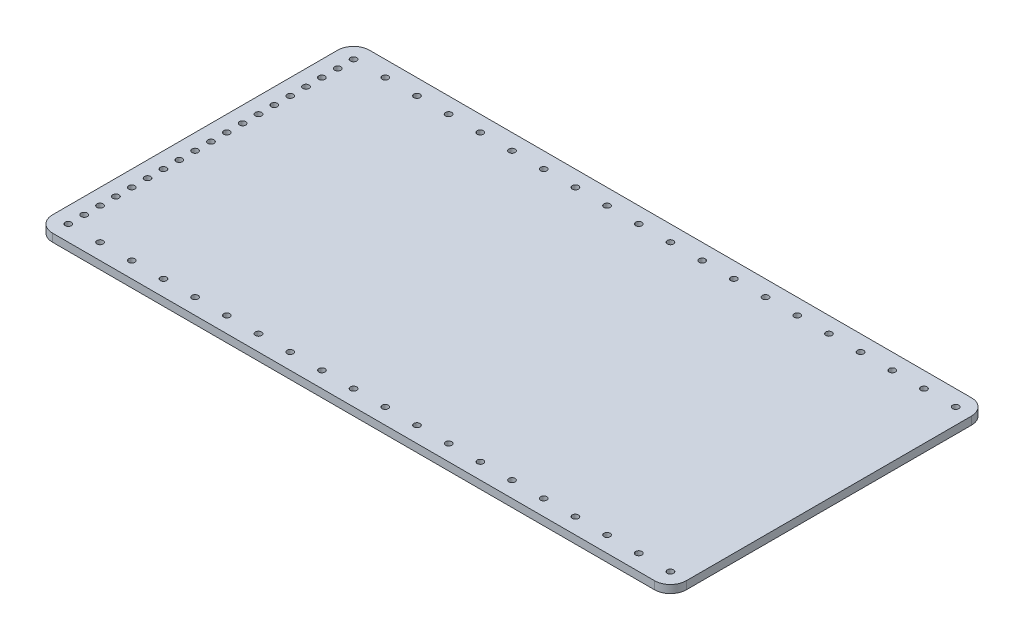
SolidWorks part; units mm, degrees
material "PC High Viscosity"
ref_plane "Front Plane" through (0, 0, 0) normal (0, 0, 1) x (1, 0, 0)
ref_plane "Top Plane" through (0, 0, 0) normal (0, 1, 0) x (1, 0, 0)
ref_plane "Right Plane" through (0, 0, 0) normal (1, 0, 0) x (0, 0, -1)
sketch "Sketch1" plane through (0, 0, 0) normal (0, 1, 0) x (1, 0, 0)
  line L1 (0, 0) -> (508, 0)
  line L2 (0, 0) -> (0, 254)
  line L3 (0, 254) -> (508, 254)
  line L4 (508, 0) -> (508, 254)
  dimension "D1" = 508
  dimension "D2" = 254
extrude "Boss-Extrude1" add sketch "Sketch1" along normal blind 6.35
sketch "Sketch3" plane through (0, 6.35, 0) normal (0, 1, 0) x (1, 0, 0)
  line L0 (508, 254) -> (0, 254) construction
  line L1 (0, 254) -> (0, 0) construction
  line L2 (12.7, 241.3) -> (38.1, 241.3) construction
  line L3 (12.7, 241.3) -> (12.7, 228.6) construction
  line L4 (12.7, 12.7) -> (38.1, 12.7) construction
  line L5 (12.7, 215.9) -> (12.7, 190.5) construction
  line L6 (495.3, 241.3) -> (495.3, 228.6) construction
  circle A0 centre (12.7, 241.3) radius 2.4892
  circle A1 centre (38.1, 241.3) radius 2.4892
  circle A2 centre (63.5, 241.3) radius 2.4892
  circle A3 centre (88.9, 241.3) radius 2.4892
  circle A4 centre (114.3, 241.3) radius 2.4892
  circle A5 centre (139.7, 241.3) radius 2.4892
  circle A6 centre (165.1, 241.3) radius 2.4892
  circle A7 centre (190.5, 241.3) radius 2.4892
  circle A8 centre (215.9, 241.3) radius 2.4892
  circle A9 centre (241.3, 241.3) radius 2.4892
  circle A10 centre (266.7, 241.3) radius 2.4892
  circle A11 centre (292.1, 241.3) radius 2.4892
  circle A12 centre (317.5, 241.3) radius 2.4892
  circle A13 centre (342.9, 241.3) radius 2.4892
  circle A14 centre (368.3, 241.3) radius 2.4892
  circle A15 centre (393.7, 241.3) radius 2.4892
  circle A16 centre (419.1, 241.3) radius 2.4892
  circle A17 centre (444.5, 241.3) radius 2.4892
  circle A18 centre (469.9, 241.3) radius 2.4892
  circle A19 centre (495.3, 241.3) radius 2.4892
  circle A23 centre (12.7, 228.6) radius 2.4892
  circle A24 centre (12.7, 215.9) radius 2.4892
  circle A25 centre (12.7, 203.2) radius 2.4892
  circle A26 centre (12.7, 190.5) radius 2.4892
  circle A27 centre (12.7, 177.8) radius 2.4892
  circle A28 centre (12.7, 165.1) radius 2.4892
  circle A29 centre (12.7, 152.4) radius 2.4892
  circle A30 centre (12.7, 139.7) radius 2.4892
  circle A31 centre (12.7, 127) radius 2.4892
  circle A32 centre (12.7, 114.3) radius 2.4892
  circle A33 centre (12.7, 101.6) radius 2.4892
  circle A56 centre (12.7, 215.9) radius 2.4892
  circle A57 centre (12.7, 190.5) radius 2.4892
  circle A58 centre (12.7, 165.1) radius 2.4892
  circle A59 centre (12.7, 139.7) radius 2.4892
  circle A60 centre (12.7, 114.3) radius 2.4892
  circle A61 centre (12.7, 88.9) radius 2.4892
  circle A62 centre (12.7, 63.5) radius 2.4892
  circle A63 centre (12.7, 38.1) radius 2.4892
  circle A64 centre (12.7, 12.7) radius 2.4892
  circle A65 centre (12.7, 88.9) radius 2.4892
  circle A66 centre (12.7, 76.2) radius 2.4892
  circle A67 centre (12.7, 63.5) radius 2.4892
  circle A68 centre (12.7, 50.8) radius 2.4892
  circle A69 centre (12.7, 38.1) radius 2.4892
  circle A70 centre (12.7, 25.4) radius 2.4892
  circle A71 centre (12.7, 12.7) radius 2.4892
  circle A72 centre (38.1, 12.7) radius 2.4892
  circle A73 centre (63.5, 12.7) radius 2.4892
  circle A74 centre (88.9, 12.7) radius 2.4892
  circle A75 centre (114.3, 12.7) radius 2.4892
  circle A76 centre (139.7, 12.7) radius 2.4892
  circle A77 centre (165.1, 12.7) radius 2.4892
  circle A78 centre (190.5, 12.7) radius 2.4892
  circle A79 centre (215.9, 12.7) radius 2.4892
  circle A80 centre (241.3, 12.7) radius 2.4892
  circle A81 centre (266.7, 12.7) radius 2.4892
  circle A82 centre (292.1, 12.7) radius 2.4892
  circle A83 centre (317.5, 12.7) radius 2.4892
  circle A84 centre (342.9, 12.7) radius 2.4892
  circle A85 centre (368.3, 12.7) radius 2.4892
  circle A86 centre (393.7, 12.7) radius 2.4892
  circle A87 centre (419.1, 12.7) radius 2.4892
  circle A88 centre (444.5, 12.7) radius 2.4892
  circle A89 centre (469.9, 12.7) radius 2.4892
  circle A90 centre (495.3, 12.7) radius 2.4892
  dimension "D1" = 12.7
  dimension "D2" = 4.9784
  dimension "D3" = 12.7
  dimension "D10" = 12.7
  dimension "D5" = 25.4
  dimension "D7" = 12.7
  dimension "D9" = 25.4
  dimension "D12" = 25.4
  dimension "D14" = 12.7
  dimension "D4" = 20
  dimension "D6" = 19
  dimension "D11" = 9
  dimension "D8" = 20
fillet "Fillet1" radius 12.7 4 edges at (508, 3.175, -254) (508, 3.175, 0) (0, 3.175, 0) (0, 3.175, -254)
extrude "Cut-Extrude2" cut sketch "Sketch3" against normal through all contours A25 | A24 | A23 | A0 | A1 | A2 | A3 | A4 | A64 | A70 | A63 | A68 | A62 | A72 | A73 | A74 | A33 | A32 | A31 | A30 | A28 | A29 | A27 | A26 | A61 | A66 | A90 | A89 | A88 | A87 | A86 | A85 | A84 | A83 | A82 | A81 | A80 | A79 | A75 | A76 | A77 | A78 | A5 | A6 | A7 | A8 | A9 | A10 | A11 | A12 | A13 | A14 | A15 | A16 | A17 | A18 | A19
sketch "Sketch4" plane through (0, 6.35, 0) normal (0, -1, 0) x (1, 0, 0)
  line L0 (0, -1059.6055) -> (0, 48940.3945) construction
  line L1 (-1066.0455, 0) -> (48933.9545, 0) construction
  point P3 (0, 0)
  point P5 (0, 0)
  point P6 (0, 0)
